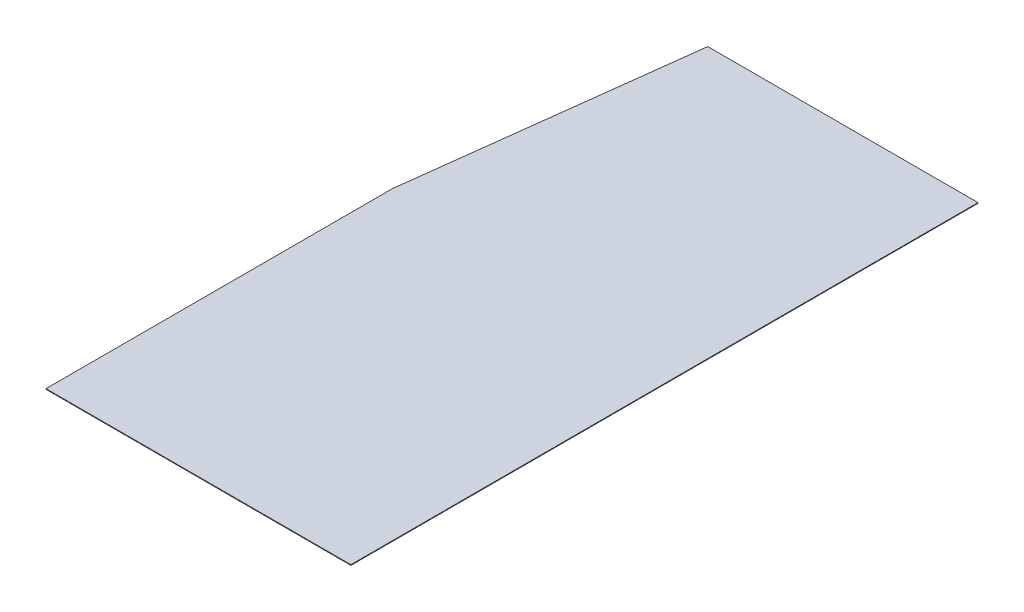
SolidWorks part; units mm, degrees
ref_plane "Alzado" through (0, 0, 0) normal (0, 0, 1) x (1, 0, 0)
ref_plane "Planta" through (0, 0, 0) normal (0, 1, 0) x (1, 0, 0)
ref_plane "Vista lateral" through (0, 0, 0) normal (1, 0, 0) x (0, 0, -1)
sketch "Croquis2" plane through (0, 0, 0) normal (0, 1, 0) x (1, 0, 0)
  line L0 (440, 0) -> (-440, 0)
  line L1 (-440, 0) -> (-440, 1000)
  line L2 (-440, 1000) -> (-340, 1810)
  line L3 (-340, 1810) -> (440, 1810)
  line L4 (440, 1810) -> (440, 0)
  dimension "D1" = 880
  dimension "D2" = 1000
  dimension "D3" = 1810
  dimension "D4" = 780
  dimension "D5" = 172.962
  dimension "D6" = 816.1495
extrude "Saliente-Extruir1" add sketch "Croquis2" along normal blind 1.9
